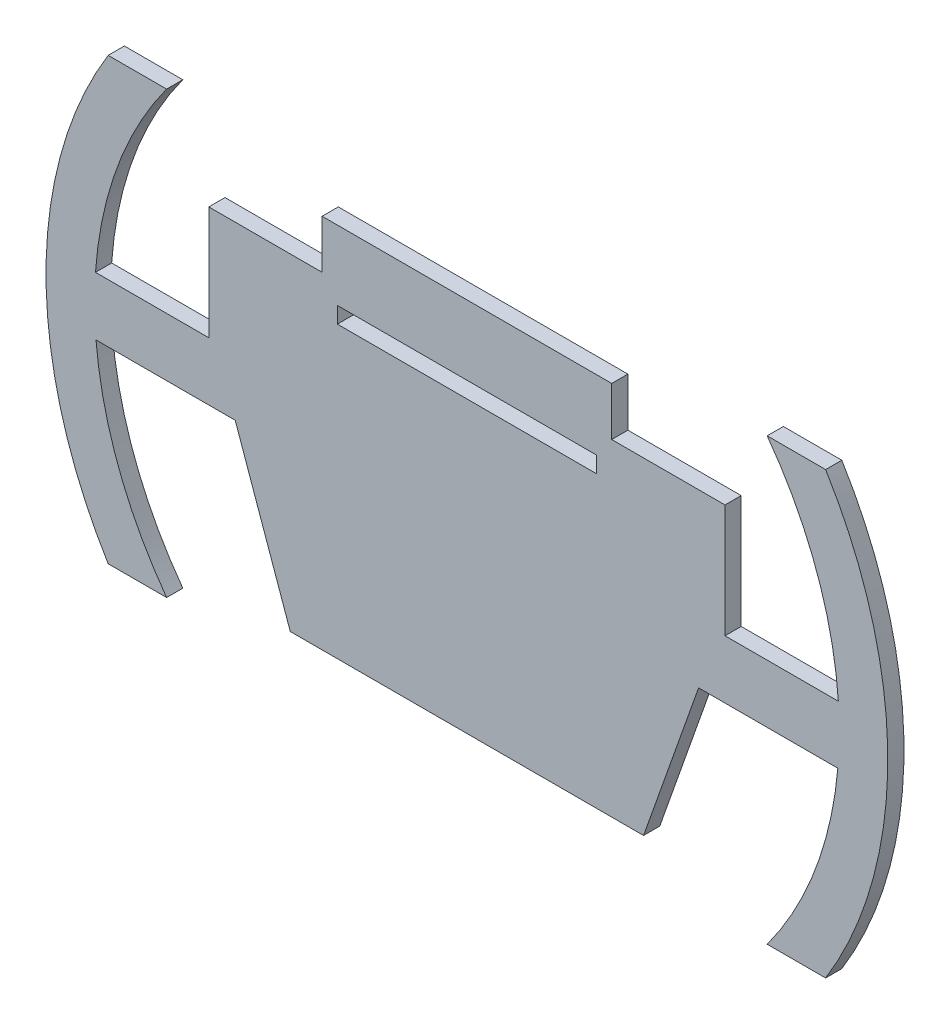
SolidWorks part; units mm, degrees
material "1.6566 (17NiCrMo6-4)"
ref_plane "Plan de face" through (0, 0, 0) normal (0, 0, 1) x (1, 0, 0)
ref_plane "Plan de dessus" through (0, 0, 0) normal (0, 1, 0) x (1, 0, 0)
ref_plane "Plan de droite" through (0, 0, 0) normal (1, 0, 0) x (0, 0, -1)
sketch "Esquisse1" plane through (0, 0, 0) normal (0, 0, 1) x (1, 0, 0)
  line L0 (0, 0) -> (296.2293, 0) construction
  line L1 (0, 0) -> (0, 97.4663) construction
  line L3 (-79.7214, -10) -> (-79.7214, 25)
  line L4 (-79.7214, 25) -> (-44.7214, 25)
  line L5 (-44.7214, 25) -> (-44.7214, 40)
  line L6 (-44.7214, 40) -> (44.7214, 40)
  line L7 (79.7214, -10) -> (114.7214, -10)
  line L8 (79.7214, -10) -> (79.7214, 25)
  line L9 (79.7214, 25) -> (44.7214, 25)
  line L10 (44.7214, 25) -> (44.7214, 40)
  line L11 (0, -18) -> (-148.6579, -18) construction
  line L12 (71.5644, -28) -> (114.5644, -28)
  line L13 (92.7416, -86) -> (110.7971, -86)
  line L20 (92.7416, 50) -> (110.7971, 50)
  line L21 (-54.56, -76) -> (54.56, -76)
  line L22 (54.56, -76) -> (71.5644, -28)
  line L23 (-79.7214, -10) -> (-114.7214, -10)
  line L25 (-54.56, -76) -> (-71.5644, -28)
  line L26 (-71.5644, -28) -> (-114.5644, -28)
  line L27 (-92.7416, 50) -> (-110.7971, 50)
  line L28 (-92.7416, -86) -> (-110.7971, -86)
  arc A1 (110.7971, 50) -> (110.7971, -86) centre (0, -18) cw
  arc A4 (-110.7971, 50) -> (-110.7971, -86) centre (0, -18) ccw
  arc A5 (-92.7416, 50) -> (-92.7416, -86) centre (0, -18) ccw
  arc A7 (92.7416, 50) -> (92.7416, -86) centre (0, -18) cw
  point P21 (0, 40)
  point P29 (0, -76)
  dimension "D2" = 35
  dimension "D11" = 115
  dimension "D14" = 54.56
  dimension "D15" = 43
  dimension "D13" = 130
  dimension "D3" = 8
  dimension "D4" = 35
  dimension "D5" = 15
  dimension "D6" = 48
  dimension "D7" = 35
  dimension "D8" = 18
  dimension "D9" = 10
  dimension "D10" = 10
  dimension "D12" = 10
extrude "Boss.-Extru.1" add sketch "Esquisse1" along normal blind 5 contours A7 L7 L8 L9 L10 L6 L5 L4 L3 L23 A5 L26 L25 L21 L22 L12 | A5 L27 A4 L28 | A7 L13 A1 L20 region at (0, -17.6129, 0) region at (-115.5141, -18, 0) region at (115.5141, -18, 0)
sketch "Esquisse2" plane through (0, 0, 5) normal (0, 0, 1) x (1, 0, 0)
  line L0 (0, 0) -> (0, 60.033) construction
  line L1 (0, 0) -> (89.5007, 0) construction
  line L2 (-44.7214, 40) -> (44.7214, 40)
  line L3 (-40, 18.5) -> (40, 18.5)
  line L4 (-40, 18.5) -> (-40, 13.5)
  line L5 (-40, 13.5) -> (40, 13.5)
  line L6 (40, 18.5) -> (40, 13.5)
  line L7 (-40, 18.5) -> (40, 13.5) construction
  line L8 (-40, 13.5) -> (40, 18.5) construction
  point P1 (0, 16)
  dimension "D1" = 80
  dimension "D2" = 5
  dimension "D3" = 21.5
extrude "Enlèv. mat.-Extru.1" cut sketch "Esquisse2" against normal blind 10 contours L6 L3 L4 L5 region at (0, 16, 5)
sketch "Esquisse3" plane through (0, 0, 5) normal (0, 0, 1) x (1, 0, 0)
  line L0 (0, 0) -> (0, 59.4514) construction
  line L1 (0, 0) -> (88.4436, 0) construction
